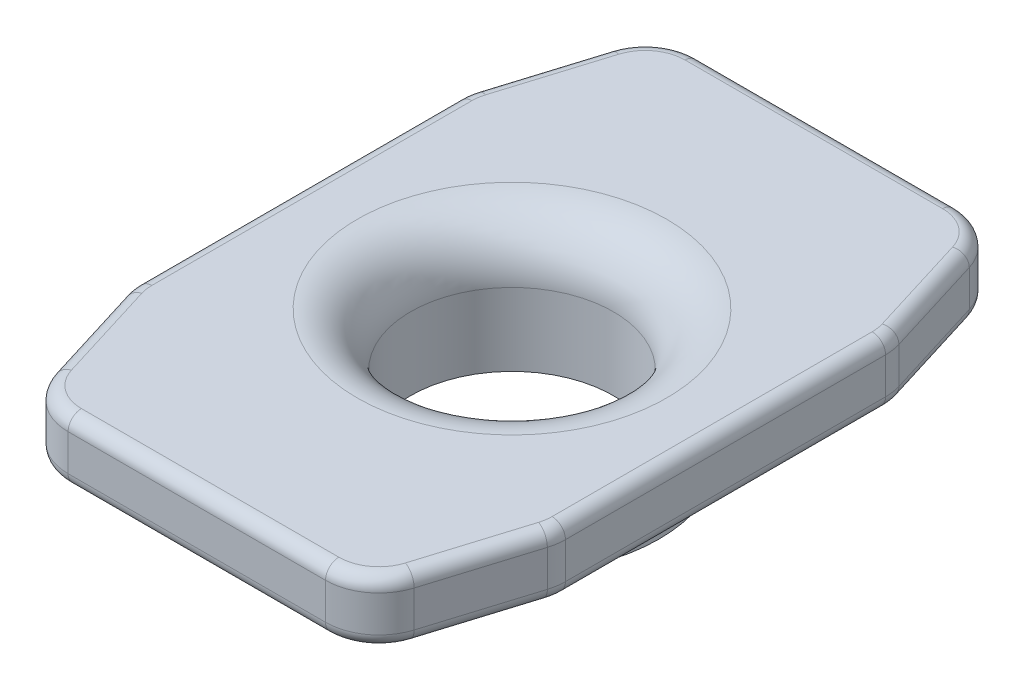
SolidWorks part; units mm, degrees
ref_plane "Front Plane" through (0, 0, 0) normal (0, 0, 1) x (1, 0, 0)
ref_plane "Top Plane" through (0, 0, 0) normal (0, 1, 0) x (1, 0, 0)
ref_plane "Right Plane" through (0, 0, 0) normal (1, 0, 0) x (0, 0, -1)
sketch "Sketch1" plane through (0, 0, 0) normal (0, 1, 0) x (1, 0, 0)
  line L0 (-4, 7.5) -> (-5.08, 4)
  line L1 (5.08, 7.5) -> (-5.08, 7.5)
  line L2 (5.08, 7.5) -> (5.08, -7.5)
  line L3 (5.08, -7.5) -> (-5.08, -7.5)
  line L4 (-5.08, 7.5) -> (-5.08, -7.5)
  line L5 (5.08, 7.5) -> (-5.08, -7.5) construction
  line L6 (5.08, -7.5) -> (-5.08, 7.5) construction
  line L7 (0, 7.5) -> (0, -7.5) construction
  line L8 (4, 7.5) -> (5.08, 4)
  line L9 (-5.08, 0) -> (5.08, 0) construction
  line L10 (4, -7.5) -> (5.08, -4)
  line L11 (-4, -7.5) -> (-5.08, -4)
  circle A0 centre (0, 0) radius 2.413
  point P0 (0, 0)
  dimension "D5" = 4.826
  dimension "D1" = 10.16
  dimension "D2" = 15
  dimension "D3" = 4
  dimension "D4" = 4
extrude "Boss-Extrude1" add sketch "Sketch1" along normal blind 1.5 contours L11 L3 L10 L2 L8 L1 L0 L4 A0 region at (0, 0, -7.3188)
sketch "Sketch2" plane through (0, 0, 0) normal (0, -1, 0) x (1, 0, 0)
  circle A0 centre (0, 0) radius 3.5
  circle A1 centre (0, 0) radius 2.413 construction
  circle A2 centre (0, 0) radius 2.413
  circle M1 centre (0, 0) radius 2.413
  dimension "D1" = 7
extrude "Boss-Extrude2" add sketch "Sketch2" along normal offset from surface (1.5 mm away) 3 contours A0 M1 region at (-3.401, 0, 0) up to face at (0, 1.5, 2.413)
fillet "Fillet1" radius 1.27 9 edges at (0, 1.5, 2.413) (4, 0.75, 7.5) (-4, 0.75, 7.5) (-5.08, 0.75, 4) (-5.08, 0.75, -4) (-4, 0.75, -7.5) (4, 0.75, -7.5) (5.08, 0.75, -4) (5.08, 0.75, 4)
fillet "Fillet2" radius 0.3175 33 edges at (5.0658, 0, -3.9979) (4.6499, 0, -5.3937) (3.8169, 0, -7.2519) (0, 0, -7.5) (-3.8169, 0, -7.2519) (-4.6499, 0, -5.3937) (-5.0658, 0, -3.9979) (-5.08, 0, 0) (-5.0658, 0, 3.9979) (-4.6499, 0, 5.3937) (-3.8169, 0, 7.2519) (0, 0, 7.5) (3.8169, 0, 7.2519) (4.6499, 0, 5.3937) (5.0658, 0, 3.9979) (3.8169, 1.5, 7.2519) (0, 1.5, 7.5) (-3.8169, 1.5, 7.2519) (-4.6499, 1.5, 5.3937) (-5.0658, 1.5, 3.9979) (-5.08, 1.5, 0) (-5.0658, 1.5, -3.9979) (-4.6499, 1.5, -5.3937) (-3.8169, 1.5, -7.2519) (0, 1.5, -7.5) (3.8169, 1.5, -7.2519) (4.6499, 1.5, -5.3937) (5.0658, 1.5, -3.9979) (5.08, 1.5, 0) (5.0658, 1.5, 3.9979) (5.08, 0, 0) (4.6499, 1.5, 5.3937) (0, 0, 3.5)
